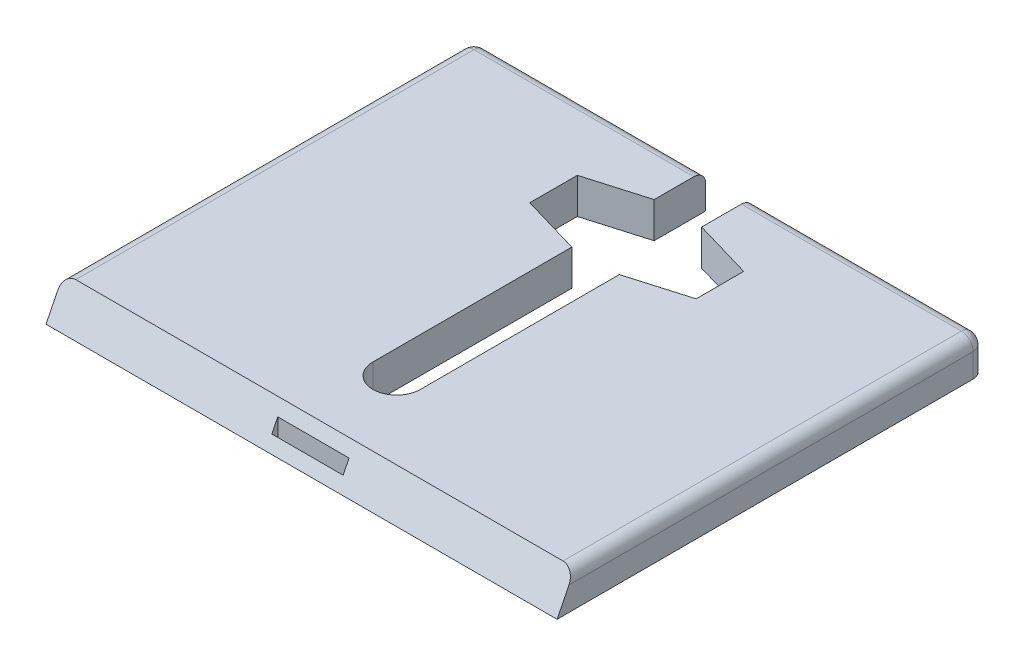
SolidWorks part; units mm, degrees
ref_plane "Ebene vorne" through (0, 0, 0) normal (0, 0, 1) x (1, 0, 0)
ref_plane "Ebene oben" through (0, 0, 0) normal (0, 1, 0) x (1, 0, 0)
ref_plane "Ebene rechts" through (0, 0, 0) normal (1, 0, 0) x (0, 0, -1)
sketch "Skizze1" plane through (0, 0, 0) normal (0, 1, 0) x (1, 0, 0)
  line L1 (-10.75, -9) -> (10.75, -9)
  line L2 (-10.75, -9) -> (-10.75, 9)
  line L3 (-10.75, 9) -> (10.75, 9)
  line L4 (10.75, -9) -> (10.75, 9)
  line L5 (-10.75, -9) -> (10.75, 9) construction
  line L6 (-10.75, 9) -> (10.75, -9) construction
  point P0 (0, 0)
  dimension "D1" = 18
  dimension "D2" = 21.5
extrude "Aufsatz-Linear austragen1" add sketch "Skizze1" along normal blind 1.5
fillet "Verrundung1" radius 0.5 3 edges at (10.75, 1.5, 0) (0, 1.5, -9) (-10.75, 1.5, 0)
sketch "Skizze2" plane through (-10.75, 0, 0) normal (-1, 0, 0) x (0, 0, 1)
  line L0 (9, 0) -> (8.25, 1.5)
  line L1 (-8.5, 1.5) -> (9, 1.5) construction
  line L2 (8.25, 1.5) -> (9, 1.5)
  line L3 (9, 1.5) -> (9, 0)
  dimension "D1" = 0.75
extrude "Schnitt-Linear austragen1" cut sketch "Skizze2" against normal up to surface (21.5 mm away) up to face at (10.75, 0.5, 0)
sketch "Skizze4" plane through (0, 1.5, 0) normal (0, 1, 0) x (1, 0, 0)
  line L6 (10.25, -8.25) -> (-10.25, -8.25) construction
  line L7 (-1.5, -8.75) -> (1.5, -8.75)
  line L8 (-1.5, -8.75) -> (-1.5, -8.5)
  line L9 (-1.5, -8.5) -> (1.5, -8.5)
  line L10 (1.5, -8.75) -> (1.5, -8.5)
  line L11 (-1.5, -8.75) -> (1.5, -8.5) construction
  line L12 (-1.5, -8.5) -> (1.5, -8.75) construction
  line L13 (-10.75, -8.5) -> (-10.75, -9) construction
  point P0 (0, -8.625)
  dimension "D1" = 0.25
  dimension "D2" = 0.25
  dimension "D3" = 3
  dimension "D4" = 10.75
extrude "Schnitt-Linear austragen2" cut sketch "Skizze4" against normal up to surface (1.5 mm away) up to face at (0, 0, 0)
fillet "Verrundung2" radius 0.5 4 edges at (10.6036, 1.3536, -8.8536) (-10.6036, 1.3536, -8.8536) (10.75, 0.5, -9) (-10.75, 0.5, -9)
sketch "Skizze5" plane through (0, 1.5, 0) normal (0, 1, 0) x (1, 0, 0)
  line L0 (-10.75, 8.5) -> (-10.75, -9) construction
  line L1 (-3.5, 4.1) -> (3.5, 4.1)
  line L2 (-3.5, 4.1) -> (-3.5, 6.1)
  line L3 (-3.5, 6.1) -> (3.5, 6.1)
  line L4 (3.5, 4.1) -> (3.5, 6.1)
  line L5 (-3.5, 4.1) -> (3.5, 6.1) construction
  line L6 (-3.5, 6.1) -> (3.5, 4.1) construction
  line L7 (-10.25, 9) -> (10.25, 9) construction
  circle A0 centre (0, 5.1) radius 2
  dimension "D2" = 4
  dimension "D1" = 7
  dimension "D3" = 2
  dimension "D4" = 10.75
  dimension "D5" = 3.9
extrude "Schlüsselloch" cut sketch "Skizze5" against normal up to surface (1.5 mm away) contours A0 L3 L2 L1 | L3 A0 | L1 A0 L3 | L1 A0 | A0 L1 L4 L3 region at (-2.7046, 1.5, -5.1) region at (0, 1.5, -5.1) region at (0, 1.5, -3.69) region at (2.7046, 1.5, -5.1) region at (0, 1.5, -6.51) up to face at (0, 0, 8.625)
sketch "Skizze6" plane through (0, 1.5, 0) normal (0, 1, 0) x (1, 0, 0)
  line L0 (0, 9) -> (0, -5) construction
  line L1 (-10.25, 9) -> (10.25, 9) construction
  line L2 (1, 9) -> (1, -5)
  line L3 (-1, 9) -> (-1, -5)
  line L5 (10.25, -8.25) -> (10.25, 8.5) construction
  arc A0 (1, 9) -> (-1, 9) centre (0, 9) ccw
  arc A1 (-1, -5) -> (1, -5) centre (0, -5) ccw
  point P4 (0, 2)
  dimension "D3" = 14
  dimension "D1" = 10.25
  dimension "D2" = 1
extrude "Langloch" cut sketch "Skizze6" against normal up to surface (1.5 mm away) up to face at (0, 0, -5.1)
sketch "Skizze7" plane through (0, 1.5, 0) normal (0, 1, 0) x (1, 0, 0)
  line L0 (3.5, 4.1) -> (1, 3.3679)
  line L1 (1, 3.3679) -> (-1, 3.3679)
  line L2 (-1, 3.3679) -> (-3.5, 4.1)
  line L3 (-3.5, 4.1) -> (-3.5, 6.1)
  line L4 (-3.5, 6.1) -> (-1, 6.8321)
  line L5 (-1, 6.8321) -> (1, 6.8321)
  line L6 (1, 6.8321) -> (3.5, 6.1)
  line L7 (3.5, 6.1) -> (3.5, 4.1)
extrude "Schnitt-Linear austragen3" cut sketch "Skizze7" against normal up to surface (1.5 mm away) up to face at (0, 0, -3.8821)
